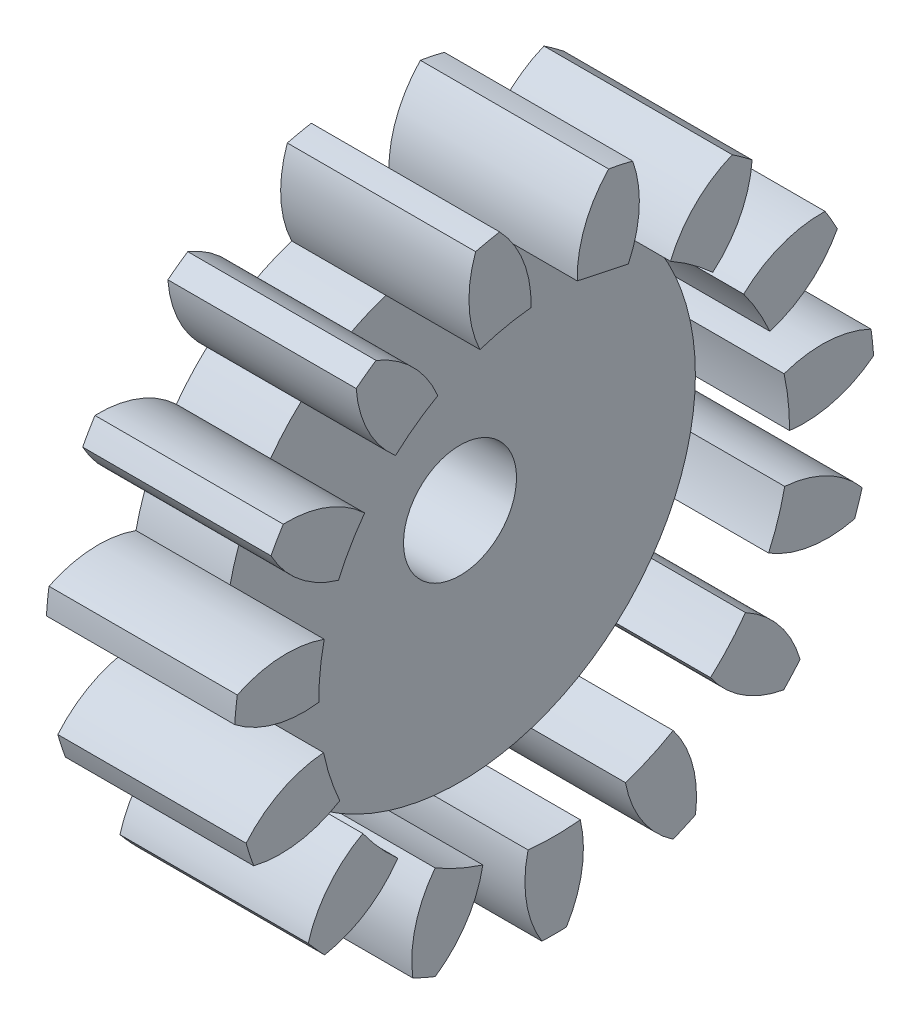
SolidWorks part; units mm, degrees
ref_plane "Plane1" through (0, 0, 0) normal (0, 0, 1) x (1, 0, 0)
ref_plane "Plane2" through (0, 0, 0) normal (0, 1, 0) x (1, 0, 0)
ref_plane "Plane3" through (0, 0, 0) normal (1, 0, 0) x (0, 0, -1)
sketch "HoldingSke" plane through (0, 0, 0) normal (0, 1, 0) x (1, 0, 0)
  line L0 (0, 0) -> (0.483, -0.1294)
  line L1 (-15, 0) -> (100, 0) construction
  line L2 (0, 0) -> (-2.1039, 2.3779)
  line L3 (0, 0) -> (-11.863, 4.5341)
  line L4 (0, 0) -> (8.3417, 2.2352)
  line L5 (0, 0) -> (-46.8476, -17.4728)
  line L6 (0, 0) -> (-4.1448, -2.7965)
  line L7 (-2.1039, 2.3779) -> (8.6586, 51.2059)
  line L8 (-76.2, 54.61) -> (-75.2, 54.61)
  line L9 (-67.7845, 28.3722) -> (-49.3413, 33.142)
  line L10 (-76.2, 71.12) -> (104.1128, 71.12)
  line L11 (0, 0) -> (-5, 0)
  line L12 (-76.2, 101.6) -> (-76.133, 101.6)
  line L13 (24.9733, 27.94) -> (52.9518, 28.4284)
  line L14 (24.9733, 27.94) -> (24.9743, 27.94)
  line L15 (24.9733, 27.94) -> (100.4006, 29.5858)
  line L16 (-63.627, -2) -> (-12.827, -2)
  circle A0 centre (0, 0) radius 3
  circle A1 centre (0, 0) radius 12.499
  circle A2 centre (0, 0) radius 37.5
  circle A3 centre (0, 0) radius 3
  dimension "Num_teeth" = 15
  dimension "Pitch_radius" = 180.3128
  dimension "Width" = 5
  dimension "Thickness" = 5
sketch "BasProSke" plane through (0, 0, 0) normal (0, 1, 0) x (1, 0, 0)
  line L0 (-10, 0) -> (60, 0) construction
  line L1 (0, 0) -> (0, 17)
  line L2 (0, 0) -> (5, 0)
  line L3 (5, 0) -> (5, 17)
  line L4 (5, 17) -> (0, 17)
  dimension "Thickness" = 5
  dimension "Diameter" = 34
revolve "Base-Revolve" add sketch "BasProSke" angle 360 about L0
sketch "TooCutSke" plane through (0, 0, 0) normal (1, 0, 0) x (0, 0, -1)
  line L1 (0, 0) -> (0, 107) construction
  line L2 (0, 0) -> (-1.6851, 14.905) construction
  line L3 (0, 0) -> (-6.2081, 29.2069) construction
  line L4 (-1.6851, 14.905) -> (-3.1041, 14.6034) construction
  arc A0 (1.2259, 12.4387) -> (-1.2259, 12.4387) centre (0, 0) ccw
  arc A1 (2.9155, 16.7739) -> (-2.9155, 16.7739) centre (0, 0) ccw
  circle A2 centre (0, 0) radius 15 construction
  circle A3 centre (0, 0) radius 14.5222 construction
  arc A4 (-1.2259, 12.4387) -> (-2.9155, 16.7739) centre (-7.2238, 12.5981) ccw
  arc A5 (2.9155, 16.7739) -> (1.2259, 12.4387) centre (7.2238, 12.5981) ccw
extrude "ToothCut" cut sketch "TooCutSke" along normal through all
fillet "Breaks" [suppressed] radius 0.04 tangent propagation no
fillet "RootFillets" [suppressed] radius 0.501
pattern_circular "TeethCuts" count 15 every 24 about axis through (-10, 0, 0) along (1, 0, 0) of "ToothCut", "RootFillets", "Breaks"
sketch "HubNeaOneSke" plane through (0, 0, 0) normal (-1, 0, 0) x (0, 0, 1)
  circle A0 centre (0, 0) radius 12.499
  dimension "Diameter" = 24.998
extrude "HubNearOne" [suppressed] add sketch "HubNeaOneSke" along normal blind 45.0001
sketch "HubNeaBotSke" plane through (0, 0, 0) normal (-1, 0, 0) x (0, 0, 1)
  circle A0 centre (0, 0) radius 12.499
  dimension "Diameter" = 24.998
extrude "HubNearBoth" [suppressed] add sketch "HubNeaBotSke" along normal blind 22.5
ref_plane "FarPln" through (5, 0, 0) normal (1, 0, 0) x (0, 0, -1)
sketch "HubFarSke" plane through (5, 0, 0) normal (1, 0, 0) x (0, 0, -1)
  circle A0 centre (0, 0) radius 12.499
  dimension "Diameter" = 24.998
extrude "HubFar" [suppressed] add sketch "HubFarSke" along normal blind 22.5
sketch "BorSke" plane through (0, 0, 0) normal (1, 0, 0) x (0, 0, -1)
  circle A0 centre (0, 0) radius 3
  dimension "Diameter" = 6
extrude "Bore" cut sketch "BorSke" along normal mid plane 100.0001
sketch "KeySke" plane through (0, 0, 0) normal (1, 0, 0) x (0, 0, -1)
  line L0 (-1, 0) -> (-1, 4)
  line L1 (-1, 4) -> (1, 4)
  line L2 (1, 4) -> (1, 0)
  line L3 (0, 0) -> (0, 34) construction
  line L4 (-1, 0) -> (1, 0)
  dimension "Width" = 2
extrude "Keyway" [suppressed] cut sketch "KeySke" along normal mid plane 100.0001
pattern_circular "Keyway2" [suppressed] count 2 every 90 about axis through (-10, 0, 0) along (1, 0, 0) reverse direction yes
sketch "Sketch1" plane through (5, 0, 0) normal (1, 0, 0) x (0, 0, -1)
  line L0 (1.2259, 12.4387) -> (3.9393, 11.862)
  line L1 (6.1792, 10.8647) -> (8.4235, 9.2342)
  line L2 (10.0641, 7.4121) -> (11.4511, 5.0097)
  line L3 (12.2088, 2.6778) -> (12.4987, -0.081)
  line L4 (12.2424, -2.5194) -> (11.3852, -5.1577)
  line L5 (10.1593, -7.2811) -> (8.3031, -9.3426)
  line L6 (6.3195, -10.7837) -> (3.7853, -11.912)
  line L7 (1.387, -12.4218) -> (-1.387, -12.4218)
  line L8 (-3.7853, -11.912) -> (-6.3195, -10.7837)
  line L9 (-8.3031, -9.3426) -> (-10.1593, -7.2811)
  line L10 (-11.3852, -5.1577) -> (-12.2424, -2.5194)
  line L11 (-12.4987, -0.081) -> (-12.2088, 2.6778)
  line L12 (-11.4511, 5.0097) -> (-10.0641, 7.4121)
  line L13 (-8.4235, 9.2342) -> (-6.1792, 10.8647)
  line L14 (-3.9393, 11.862) -> (-1.2259, 12.4387)
  circle A0 centre (0, 0) radius 12.5
  arc A1 (2.8942, 16.7518) -> (1.2259, 12.4387) centre (7.2238, 12.5981) ccw construction
  arc A2 (2.8942, 16.7518) -> (1.2259, 12.4387) centre (7.2238, 12.5981) ccw
  arc A3 (4.1696, 16.4807) -> (2.8942, 16.7518) centre (0, 0) ccw construction
  arc A4 (4.1696, 16.4807) -> (2.8942, 16.7518) centre (0, 0) ccw
  arc A5 (3.9393, 11.862) -> (4.1696, 16.4807) centre (-1.4752, 14.4471) ccw construction
  arc A6 (3.9393, 11.862) -> (4.1696, 16.4807) centre (-1.4752, 14.4471) ccw
  arc A7 (8.4235, 9.2342) -> (10.5125, 13.3599) centre (4.5285, 13.7981) ccw
  arc A8 (10.5125, 13.3599) -> (9.4575, 14.1264) centre (0, 0) ccw
  arc A9 (9.4575, 14.1264) -> (6.1792, 10.8647) centre (11.7234, 8.5707) ccw
  arc A10 (11.4511, 5.0097) -> (15.0376, 7.9291) centre (9.7492, 10.7633) ccw
  arc A11 (15.0376, 7.9291) -> (14.3856, 9.0584) centre (0, 0) ccw
  arc A12 (14.3856, 9.0584) -> (10.0641, 7.4121) centre (14.1959, 3.0614) ccw
  arc A13 (12.4987, -0.081) -> (16.9626, 1.1273) centre (13.2841, 5.8674) ccw
  arc A14 (16.9626, 1.1273) -> (16.8263, 2.4241) centre (0, 0) ccw
  arc A15 (16.8263, 2.4241) -> (12.2088, 2.6778) centre (14.2137, -2.9773) ccw
  arc A16 (11.3852, -5.1577) -> (15.9546, -5.8695) centre (14.5222, -0.043) ccw
  arc A17 (15.9546, -5.8695) -> (16.3575, -4.6293) centre (0, 0) ccw
  arc A18 (16.3575, -4.6293) -> (12.2424, -2.5194) centre (11.7739, -8.5011) ccw
  arc A19 (8.3031, -9.3426) -> (12.1879, -11.8514) centre (13.2492, -5.946) ccw
  arc A20 (12.1879, -11.8514) -> (13.0604, -10.8823) centre (0, 0) ccw
  arc A21 (13.0604, -10.8823) -> (10.1593, -7.2811) centre (7.2983, -12.555) ccw
  arc A22 (3.7853, -11.912) -> (6.3138, -15.784) centre (9.6853, -10.8208) ccw
  arc A23 (6.3138, -15.784) -> (7.5051, -15.2537) centre (0, 0) ccw
  arc A24 (7.5051, -15.2537) -> (6.3195, -10.7837) centre (1.5607, -14.4381) ccw
  arc A25 (-1.387, -12.4218) -> (-0.652, -16.9875) centre (4.4467, -13.8247) ccw
  arc A26 (-0.652, -16.9875) -> (0.652, -16.9875) centre (0, 0) ccw
  arc A27 (0.652, -16.9875) -> (1.387, -12.4218) centre (-4.4467, -13.8247) ccw
  arc A28 (-6.3195, -10.7837) -> (-7.5051, -15.2537) centre (-1.5607, -14.4381) ccw
  arc A29 (-7.5051, -15.2537) -> (-6.3138, -15.784) centre (0, 0) ccw
  arc A30 (-6.3138, -15.784) -> (-3.7853, -11.912) centre (-9.6853, -10.8208) ccw
  arc A31 (-10.1593, -7.2811) -> (-13.0604, -10.8823) centre (-7.2983, -12.555) ccw
  arc A32 (-13.0604, -10.8823) -> (-12.1879, -11.8514) centre (0, 0) ccw
  arc A33 (-12.1879, -11.8514) -> (-8.3031, -9.3426) centre (-13.2492, -5.946) ccw
  arc A34 (-12.2424, -2.5194) -> (-16.3575, -4.6293) centre (-11.7739, -8.5011) ccw
  arc A35 (-16.3575, -4.6293) -> (-15.9546, -5.8695) centre (0, 0) ccw
  arc A36 (-15.9546, -5.8695) -> (-11.3852, -5.1577) centre (-14.5222, -0.043) ccw
  arc A37 (-12.2088, 2.6778) -> (-16.8263, 2.4241) centre (-14.2137, -2.9773) ccw
  arc A38 (-16.8263, 2.4241) -> (-16.9626, 1.1273) centre (0, 0) ccw
  arc A39 (-16.9626, 1.1273) -> (-12.4987, -0.081) centre (-13.2841, 5.8674) ccw
  arc A40 (-10.0641, 7.4121) -> (-14.3856, 9.0584) centre (-14.1959, 3.0614) ccw
  arc A41 (-14.3856, 9.0584) -> (-15.0376, 7.9291) centre (0, 0) ccw
  arc A42 (-15.0376, 7.9291) -> (-11.4511, 5.0097) centre (-9.7492, 10.7633) ccw
  arc A43 (-6.1792, 10.8647) -> (-9.4575, 14.1264) centre (-11.7234, 8.5707) ccw
  arc A44 (-9.4575, 14.1264) -> (-10.5125, 13.3599) centre (0, 0) ccw
  arc A45 (-10.5125, 13.3599) -> (-8.4235, 9.2342) centre (-4.5285, 13.7981) ccw
  arc A46 (-1.2259, 12.4387) -> (-2.8942, 16.7518) centre (-7.2238, 12.5981) ccw
  arc A47 (-2.8942, 16.7518) -> (-4.1696, 16.4807) centre (0, 0) ccw
  arc A48 (-4.1696, 16.4807) -> (-3.9393, 11.862) centre (1.4752, 14.4471) ccw
  dimension "D1" = 15
extrude "Boss-Extrude1" add sketch "Sketch1" along normal blind 5 contours A8 A9 A0 A7 | A11 A12 A0 A10 | A14 A15 A0 A13 | A17 A18 A0 A16 | A20 A21 A0 A19 | A23 A24 A0 A22 | A26 A27 A0 A25 | A29 A30 A0 A28 | A32 A33 A0 A31 | A35 A36 A0 A34 | A38 A39 A0 A37 | A41 A42 A0 A40 | A44 A45 A0 A43 | A47 A48 A0 A46 | L0 A6 A4 A2 region at (5, 14.2116, 3.0208) region at (5, 11.7543, -8.54) region at (5, 11.7543, 8.54) region at (5, 7.2646, -12.5826) region at (5, 7.2646, 12.5826) region at (5, 1.5187, -14.4496) region at (5, 1.5187, 14.4496) region at (5, -4.4898, -13.818) region at (5, -4.4898, 13.818) region at (5, -9.7219, -10.7973) region at (5, -9.7219, 10.7973) region at (5, -13.273, -5.9095) region at (5, -13.273, 5.9095) region at (5, -14.5291, 0)
equation "' \"Module@HoldingSke\" = 6.35"
equation "' \"Num_teeth@HoldingSke\" = 12"
equation "' \"Ap@HoldingSke\" =  20"
equation "' \"Ap@HoldingSke\" = 20"
equation "' \"Width@HoldingSke\" = 0.5 * 25.4"
equation "' \"Hub_dia@HoldingSke\"= 1 * 25.4"
equation "' \"Hub_dia@HoldingSke\" = 1 * 25.4"
equation "' \"Overall_len@HoldingSke\" = 1.0 * 25.4"
equation "' \"Bore@HoldingSke\" = 0.75 * 25.4"
equation "' \"T_dim@HoldingSke\" = 0.1 * 25.4"
equation "' \"Width@KeySke\" = 0.25 * 25.4"
equation "' \"Show_teeth@HoldingSke\" = 13"
equation "' \"Backlash@HoldingSke\" = 0.009 * 25.4"
equation "' \"Addendum_fac@HoldingSke\" = 1.0"
equation "' \"Dedendum_fac@HoldingSke\" = 1.25"
equation "' \"Dedendum_add@HoldingSke\" = 0.00005 * 25.4"
equation "' \"Clearance_fac@HoldingSke\" = 0.25"
equation "\"Pitch@HoldingSke\" = 1 / \"Module@HoldingSke\""
equation "\"Overcut_dia@TooCutSke\" = (\"Num_teeth@HoldingSke\" + 2 * \"Addendum_fac@HoldingSke\") / \"Pitch@HoldingSke\" + 0.002 * 25.4"
equation "\"Pitch_dia@TooCutSke\" = \"Num_teeth@HoldingSke\" / \"Pitch@HoldingSke\""
equation "\"Base_dia@TooCutSke\" = \"Num_teeth@HoldingSke\" / \"Pitch@HoldingSke\" * cos((\"Ap@HoldingSke\"  * 3.14159265 / 180))"
equation "\"Root_dia@TooCutSke\" = (\"Num_teeth@HoldingSke\" + 2) / \"Pitch@HoldingSke\" - 2 * (\"Addendum_fac@HoldingSke\" + \"Dedendum_fac@HoldingSke\") / \"Pitch@HoldingSke\" - \"Dedendum_add@HoldingSke\" * 2"
equation "\"Half_ang@TooCutSke\" = 180 / \"Num_teeth@HoldingSke\""
equation "\"Half_CT@TooCutSke\" = \"Num_teeth@HoldingSke\" / \"Pitch@HoldingSke\" * sin((3.14159265 / 2 / \"Num_teeth@HoldingSke\")) / 2 - 7 * \"Backlash@HoldingSke\" / 4"
equation "\"Flank_rad@TooCutSke\" = \"Num_teeth@HoldingSke\" / \"Pitch@HoldingSke\" / 5"
equation "\"Radius@RootFillets\" = \"Clearance_fac@HoldingSke\" / \"Pitch@HoldingSke\" + \"Dedendum_add@HoldingSke\""
equation "\"Break_rad@Breaks\" = 0.02 / \"Pitch@HoldingSke\""
equation "\"Thickness@HoldingSke\" = \"Width@HoldingSke\""
equation "\"OAL@HoldingSke\" = \"Thickness@HoldingSke\""
equation "\"MHD@HoldingSke\" = (\"Num_teeth@HoldingSke\" + 2) / \"Pitch@HoldingSke\" - 2 * (\"Addendum_fac@HoldingSke\" + \"Dedendum_fac@HoldingSke\")  / \"Pitch@HoldingSke\" - \"Dedendum_add@HoldingSke\" * 2"
equation "\"MBD@HoldingSke\" = (\"Num_teeth@HoldingSke\" + 2) / \"Pitch@HoldingSke\" - 2 * (\"Addendum_fac@HoldingSke\" + \"Dedendum_fac@HoldingSke\")  / \"Pitch@HoldingSke\" - \"Dedendum_add@HoldingSke\" * 2 - 0.002 * 25.4"
equation "\"MHD@HoldingSke\" = ((sgn( \"MHD@HoldingSke\" - \"Hub_dia@HoldingSke\" )-1)*( \"MHD@HoldingSke\" - \"Hub_dia@HoldingSke\" ))/-2+ \"Hub_dia@HoldingSke\""
equation "\"MBD@HoldingSke\" = ((sgn( \"MBD@HoldingSke\" - \"Bore@HoldingSke\" )-1)*( \"MBD@HoldingSke\" - \"Bore@HoldingSke\" ))/-2+ \"Bore@HoldingSke\""
equation "\"OAL@HoldingSke\" = ((sgn( \"OAL@HoldingSke\" - \"Overall_len@HoldingSke\" )+1)*( \"OAL@HoldingSke\" - \"Overall_len@HoldingSke\" ))/2 + \"Overall_len@HoldingSke\" + 0.000002 * 25.4"
equation "\"Num_teeth@TeethCuts\" = int( \"Show_teeth@HoldingSke\" ) + 1"
equation "\"Num_teeth@TeethCuts\" = ((sgn( \"Num_teeth@TeethCuts\" - \"Num_teeth@HoldingSke\" )-1)*( \"Num_teeth@TeethCuts\" - \"Num_teeth@HoldingSke\" ))/-2+ \"Num_teeth@HoldingSke\""
equation "\"Num_teeth@TeethCuts\" = ((sgn( \"Num_teeth@TeethCuts\" - 2.0)+1)*( \"Num_teeth@TeethCuts\" - 2.0))/2 +2.0"
equation "\"Angle@TeethCuts\" = 360.0 / \"Num_teeth@HoldingSke\""
equation "\"Diameter@BasProSke\" = (\"Num_teeth@HoldingSke\" + 2 * \"Addendum_fac@HoldingSke\") / \"Pitch@HoldingSke\""
equation "\"Thickness@BasProSke\"  = \"Thickness@HoldingSke\""
equation "' \"Fillet_rad@BasProSke\" =  \"Thickness@HoldingSke\" * 0.05"
equation "' \"Fillet_rad@BasProSke\" = \"Thickness@HoldingSke\" * 0.05"
equation "\"MHD@HoldingSke\" = ((sgn( \"MHD@HoldingSke\" - \"Root_dia@TooCutSke\" )-1)*( \"MHD@HoldingSke\" - \"Root_dia@TooCutSke\" ))/-2+ \"Root_dia@TooCutSke\""
equation "\"Diameter@HubNeaOneSke\" = \"MHD@HoldingSke\""
equation "\"Length@HubNearOne\" = \"OAL@HoldingSke\" - \"Thickness@BasProSke\""
equation "\"Diameter@HubNeaBotSke\" = \"MHD@HoldingSke\""
equation "\"Length@HubNearBoth\" = ( \"OAL@HoldingSke\" - \"Thickness@BasProSke\" ) / 2.0"
equation "\"Thickness@FarPln\" = \"Thickness@BasProSke\""
equation "\"Diameter@HubFarSke\" = \"MHD@HoldingSke\""
equation "\"Length@HubFar\" = ( \"OAL@HoldingSke\" - \"Thickness@BasProSke\" ) / 2.0"
equation "\"Diameter@BorSke\" = \"MBD@HoldingSke\""
equation "\"D1@Bore\" = \"OAL@HoldingSke\" * 2.0"
equation "\"D1@Keyway\" = \"OAL@HoldingSke\" * 2.0"
equation "\"Offset@KeySke\" = \"T_dim@HoldingSke\" + \"MBD@HoldingSke\" / 2.0"
